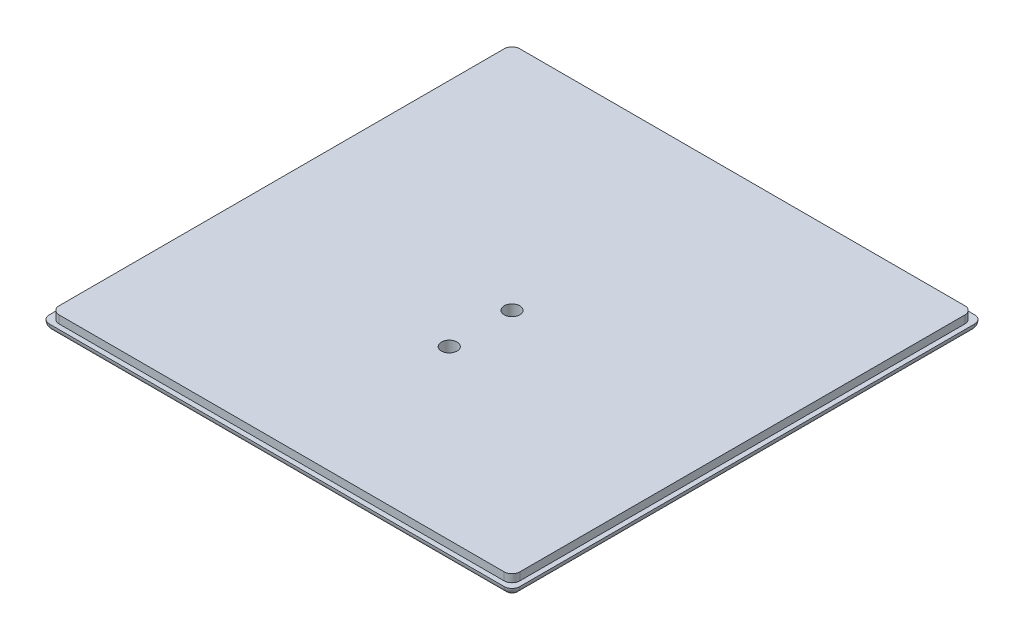
SolidWorks part; units mm, degrees
ref_plane "Front Plane" through (0, 0, 0) normal (0, 0, 1) x (1, 0, 0)
ref_plane "Top Plane" through (0, 0, 0) normal (0, 1, 0) x (1, 0, 0)
ref_plane "Right Plane" through (0, 0, 0) normal (1, 0, 0) x (0, 0, -1)
sketch "Sketch1" plane through (0, 0, 0) normal (0, 1, 0) x (1, 0, 0)
  line L1 (-60, -60) -> (60, -60)
  line L2 (-60, -60) -> (-60, 60)
  line L3 (-60, 60) -> (60, 60)
  line L4 (60, -60) -> (60, 60)
  line L5 (-60, -60) -> (60, 60) construction
  line L6 (-60, 60) -> (60, -60) construction
  point P0 (0, 0)
  dimension "D1" = 120
  dimension "D2" = 120
extrude "Boss-Extrude1" add sketch "Sketch1" along normal blind 2
sketch "Sketch2" plane through (0, 2, 0) normal (0, 1, 0) x (1, 0, 0)
  line L1 (-58.75, -58.75) -> (58.75, -58.75)
  line L2 (-58.75, -58.75) -> (-58.75, 58.75)
  line L3 (-58.75, 58.75) -> (58.75, 58.75)
  line L4 (58.75, -58.75) -> (58.75, 58.75)
  line L5 (-58.75, -58.75) -> (58.75, 58.75) construction
  line L6 (-58.75, 58.75) -> (58.75, -58.75) construction
  point P0 (0, 0)
  dimension "D1" = 117.5
  dimension "D2" = 117.5
extrude "Boss-Extrude2" add sketch "Sketch2" along normal blind 2
fillet "Fillet1" radius 2 8 edges at (-58.75, 3, -58.75) (58.75, 3, -58.75) (58.75, 3, 58.75) (-58.75, 3, 58.75) (-60, 0, 0) (0, 0, 60) (0, 0, -60) (60, 0, 0)
sketch "Sketch4" plane through (0, 0, 0) normal (0, -1, 0) x (1, 0, 0)
  circle A0 centre (0, 0) radius 2
  circle A1 centre (0, 16) radius 2
  point P5 (-8.2794, 13.6913)
  dimension "D1" = 4
  dimension "D2" = 4
  dimension "D3" = 16
extrude "Cut-Extrude1" cut sketch "Sketch4" against normal through all
